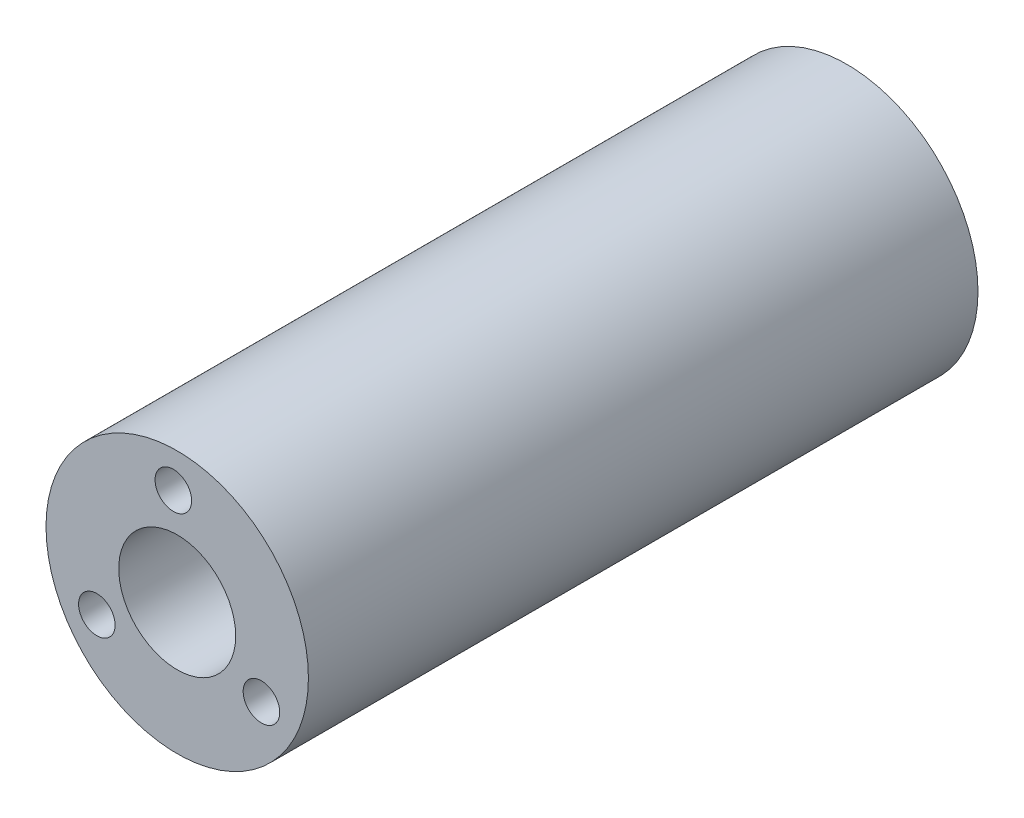
SolidWorks part; units mm, degrees
material "6061 Alloy"
ref_plane "Front Plane" through (0, 0, 0) normal (0, 0, 1) x (1, 0, 0)
ref_plane "Top Plane" through (0, 0, 0) normal (0, 1, 0) x (1, 0, 0)
ref_plane "Right Plane" through (0, 0, 0) normal (1, 0, 0) x (0, 0, -1)
sketch "Sketch1" plane through (0, 0, 0) normal (0, 0, 1) x (1, 0, 0)
  circle A0 centre (0, 0) radius 8.975
  circle A1 centre (-0.2651, 6.5) radius 1.25
  circle A2 centre (-5.4966, -3.4796) radius 1.25
  circle A3 centre (5.7617, -3.0204) radius 1.25
  circle A4 centre (0, 0) radius 4
  dimension "D1" = 17.95
  dimension "D2" = 2.5
  dimension "D3" = 8
extrude "Boss-Extrude1" add sketch "Sketch1" along normal blind 45.8
